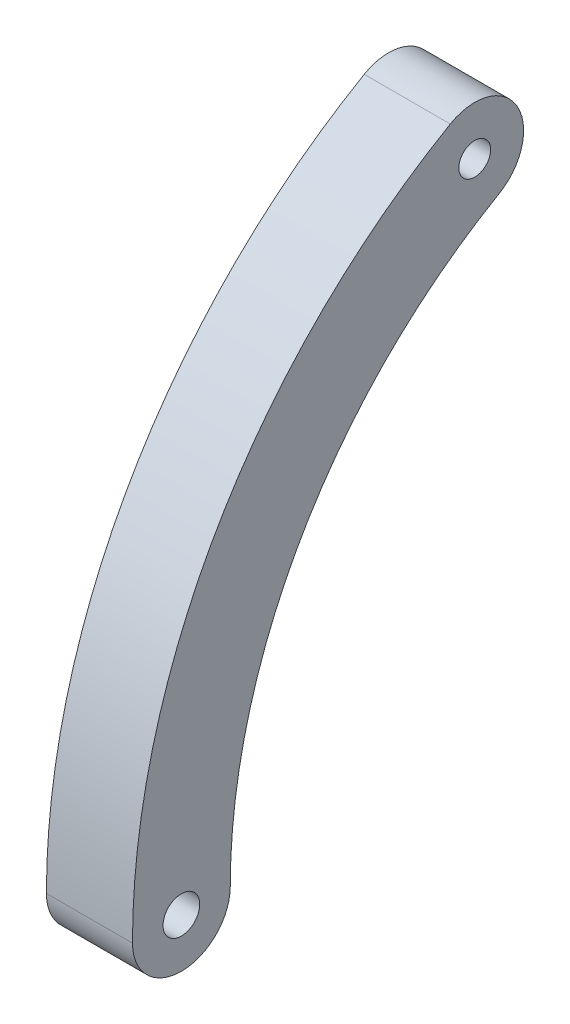
SolidWorks part; units mm, degrees
material "ABS"
ref_plane "Front Plane" through (0, 0, 0) normal (0, 0, 1) x (1, 0, 0)
ref_plane "Top Plane" through (0, 0, 0) normal (0, 1, 0) x (1, 0, 0)
ref_plane "Right Plane" through (0, 0, 0) normal (1, 0, 0) x (0, 0, -1)
sketch "Esquisse1" plane through (0, 0, 0) normal (1, 0, 0) x (0, 0, -1)
  arc A0 (-34.925, 0) -> (-17.4625, 30.2459) centre (0, 0) cw
  arc A1 (-41.275, 0) -> (-20.6375, 35.7452) centre (0, 0) cw
  arc A2 (-41.275, 0) -> (-34.925, 0) centre (-38.1, 0) ccw
  arc A3 (-17.4625, 30.2459) -> (-20.6375, 35.7452) centre (-19.05, 32.9956) ccw
  circle A4 centre (-38.1, 0) radius 1.1906
  circle A5 centre (-19.05, 32.9956) radius 1.0319
  dimension "D1" = 3.175
  dimension "D4" = 2.3812
  dimension "D5" = 2.0638
  dimension "D2" = 38.1
  dimension "D3" = 38.1
extrude "Boss.-Extru.1" add sketch "Esquisse1" along normal blind 5.588
